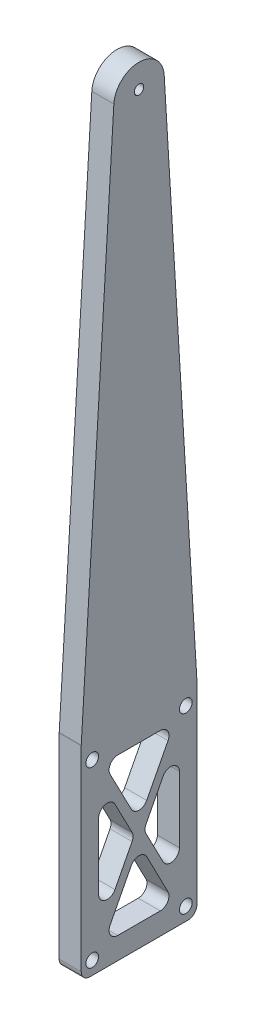
SolidWorks part; units mm, degrees
material "6061 Alloy"
ref_plane "Front Plane" through (0, 0, 0) normal (0, 0, 1) x (1, 0, 0)
ref_plane "Top Plane" through (0, 0, 0) normal (0, 1, 0) x (1, 0, 0)
ref_plane "Right Plane" through (0, 0, 0) normal (1, 0, 0) x (0, 0, -1)
sketch "Sketch1" plane through (0, 0, 0) normal (1, 0, 0) x (0, 0, -1)
  line L0 (-13.4747, 0) -> (13.4747, 0) construction
  line L1 (0, 0) -> (0, 160) construction
  line L2 (-13.4747, 0) -> (0, 160) construction
  line L3 (0, 160) -> (13.4747, 0) construction
  line L4 (13.4747, 0) -> (-13.4747, 0) construction
  line L8 (-13.4747, 0) -> (13.4747, 0) construction
  line L9 (-13.4747, 0) -> (-13.4747, -50) construction
  line L10 (13.4747, 0) -> (13.4747, -50) construction
  line L11 (-13.4747, -50) -> (13.4747, -50) construction
  line L16 (-16.645, -53.81) -> (16.645, -53.81)
  line L17 (-16.645, -53.81) -> (-16.645, 5.15)
  line L18 (16.645, -53.81) -> (16.645, 5.15)
  line L19 (-16.645, 5.15) -> (16.645, 5.15)
  line L20 (-16.645, 5.15) -> (-7.2492, 160.4386)
  line L21 (-7.2492, 160.4386) -> (7.2492, 160.4386) construction
  line L22 (7.2492, 160.4386) -> (16.645, 5.15)
  circle A0 centre (-13.4747, 0) radius 1.8288
  circle A1 centre (0, 160) radius 4.7625 construction
  circle A2 centre (13.4747, 0) radius 1.8288
  circle A3 centre (-13.4747, -50) radius 1.8288
  circle A4 centre (13.4747, -50) radius 1.8288
  arc A5 (-7.2492, 160.4386) -> (7.2492, 160.4386) centre (0, 160) cw
  point P4 (0, 0)
  point P7 (0, -53.81)
  dimension "D3" = 3.6576
  dimension "D4" = 9.525
  dimension "D9" = 2.5
  dimension "D1" = 26.9494
  dimension "D5" = 50
  dimension "D6" = 3.81
  dimension "D7" = 160
  dimension "D8" = 5.15
  dimension "D2" = 33.29
extrude "Boss-Extrude1" add sketch "Sketch1" along normal mid plane 6.35 contours A5 L20 L19 L22 | L19 L17 L16 L18 A4 A3 A2 A0 region at (0, -24.3153, 0) region at (0, 74.449, 0)
sketch "Sketch2" plane through (3.175, 0, 0) normal (1, 0, 0) x (0, 0, -1)
  line L3 (-11.645, -47.5) -> (-11.645, -2.5)
  line L4 (11.645, -47.5) -> (11.645, -2.5)
  line L5 (-11.645, -2.5) -> (11.645, -2.5)
  line L6 (-11.645, -47.5) -> (11.645, -47.5)
  line L7 (-11.645, -47.5) -> (11.645, -2.5) construction
  line L8 (-16.645, -53.81) -> (-16.645, 5.15) construction
  line L15 (11.645, -47.5) -> (-11.645, -2.5) construction
  line L24 (16.645, -53.81) -> (16.645, 5.15) construction
  line L31 (11.645, -44.7805) -> (-10.2375, -2.5)
  line L32 (-10.2375, -47.5) -> (11.645, -5.2195)
  line L33 (10.2375, -47.5) -> (-11.645, -5.2195)
  line L34 (-11.645, -44.7805) -> (10.2375, -2.5)
  line L35 (12.7551, -46.9254) -> (-10.5349, -1.9254) construction
  line L36 (10.5349, -48.0746) -> (-12.7551, -3.0746) construction
  line L37 (-10.5349, -48.0746) -> (12.7551, -3.0746) construction
  line L38 (-12.7551, -46.9254) -> (10.5349, -1.9254) construction
  circle A0 centre (13.4747, -50) radius 1.8288 construction
  circle A1 centre (13.4747, 0) radius 1.8288 construction
  point P0 (11.645, -25)
  point P2 (0, -47.5)
  point P28 (0, -25)
  dimension "D4" = 2.5
  dimension "D1" = 5
  dimension "D2" = 5
  dimension "D3" = 2.5
  dimension "D5" = 1.25
  dimension "D6" = 1.25
extrude "Cut-Extrude1" cut sketch "Sketch2" against normal through all contours L32 L31 L4 | L6 L33 L32 | L3 L34 L33 | L31 L34 L5 region at (3.175, -25, 8.2325) region at (3.175, -40.9065, 0) region at (3.175, -9.0935, 0) region at (3.175, -25, -8.2325)
fillet "Fillet1" radius 2.5 12 edges at (0, -2.5, -10.2375) (0, -22.2805, 0) (0, -2.5, 10.2375) (0, -5.2195, -11.645) (0, -44.7805, -11.645) (0, -25, -1.4075) (0, -47.5, 10.2375) (0, -47.5, -10.2375) (0, -27.7195, 0) (0, -25, 1.4075) (0, -5.2195, 11.645) (0, -44.7805, 11.645)
fillet "Fillet2" radius 2.5 4 edges at (0, 5.15, 16.645) (0, 5.15, -16.645) (0, -53.81, -16.645) (0, -53.81, 16.645)
hole_wizard "#6-32 Tapped Hole1" positions "Sketch3" profile "Sketch4" tap size "#6-32" standard "ANSI Inch" end condition through all
sketch "Sketch3" plane through (3.175, 0, 0) normal (1, 0, 0) x (0, 0, -1)
  line L0 (-7.2492, 160.4386) -> (7.2492, 160.4386) construction
  point P0 (0, 160.4386)
sketch "Sketch4" plane through (3.175, 160.4386, 0) normal (0, 1, 0) x (0, 0, -1)
  line L0 (0, 0) -> (0, 6.35)
  line L1 (0, 6.35) -> (1.3525, 6.35)
  line L2 (1.3525, 6.35) -> (1.3525, 0)
  line L5 (1.3525, 0) -> (0, 0)
  line L11 (0, -6.35) -> (0, 107.95) construction
  dimension "Thru Tap Drill Dia." = 2.7051
  dimension "Thru Tap Drill Depth" = 6.35
